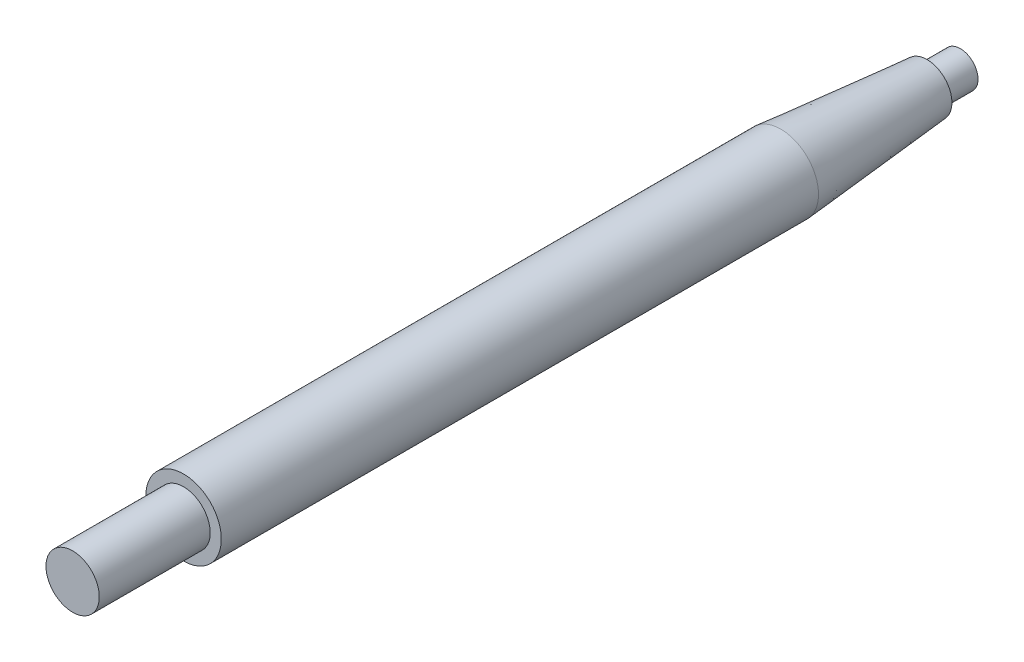
SolidWorks part; units mm, degrees
material "Plain Carbon Steel"
ref_plane "Front Plane" through (0, 0, 0) normal (0, 0, 1) x (1, 0, 0)
ref_plane "Top Plane" through (0, 0, 0) normal (0, 1, 0) x (1, 0, 0)
ref_plane "Right Plane" through (0, 0, 0) normal (1, 0, 0) x (0, 0, -1)
sketch "Base Sketch" plane through (0, 0, 0) normal (0, 1, 0) x (1, 0, 0)
  line L0 (-11.2254, 153.9926) -> (-12.8435, 153.9926)
  line L11 (-8.3435, 121.0526) -> (-11.2254, 153.9926)
  line L14 (-12.8435, 161.4926) -> (-16.8435, 161.4926)
  line L15 (-16.8435, 161.4926) -> (-16.8435, -13.5074)
  line L16 (-12.8435, 153.9926) -> (-12.8435, 161.4926)
  line L17 (-8.3435, -13.5074) -> (-10.8435, -13.5074)
  line L18 (-10.8435, -13.5074) -> (-10.8435, -38.5074)
  line L19 (-10.8435, -38.5074) -> (-16.8435, -38.5074)
  line L20 (-16.8435, -38.5074) -> (-16.8435, -13.5074)
  line L26 (-8.3435, 121.0526) -> (-8.3435, -13.5074)
  dimension "D1" = 8.5
  dimension "D3" = 32.94
  dimension "D4" = 7.5
  dimension "D6" = 4
  dimension "D5" = 6
  dimension "D7" = 25
  dimension "D8" = 200
  dimension "D2" = 185
revolve "Revolve1" add sketch "Base Sketch" angle 360 about L15
cosmetic thread "Pump Mounting Threads" parameters "D2"=6.619
cosmetic thread "Motor Mounting Threads" parameters "D2"=9.6012
equation "\"Pump_Length\"= 33.94mm"
equation "\"Shaft_Length\"= 200mm"
equation "\"D3@Base Sketch\"=\"Pump_Length\" - 1"
equation "\"D8@Base Sketch\"=\"Shaft_Length\""
equation "\"Motor_Shaft_ID\"= 12mm"
equation "\"D5@Base Sketch\"=\"Motor_Shaft_ID\"/2"
equation "\"Motor_Shaft_Length\"= 25mm"
equation "\"D7@Base Sketch\"=\"Motor_Shaft_Length\""
equation "\"Casing_Length\"= 90mm"
equation "\"Shoulder_Diameter\"= 23mm"
